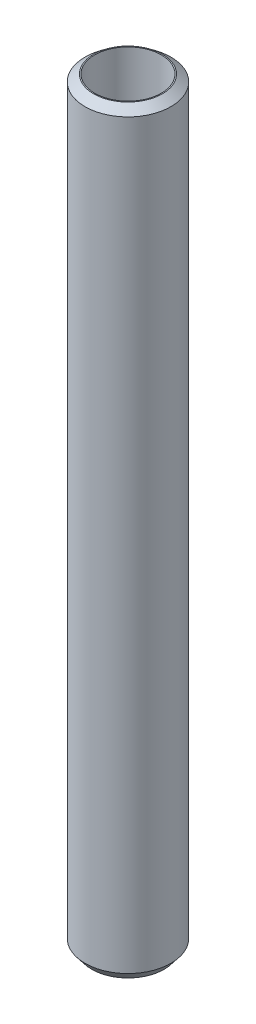
SolidWorks part; units mm, degrees
ref_plane "Front Plane" through (0, 0, 0) normal (0, 0, 1) x (1, 0, 0)
ref_plane "Top Plane" through (0, 0, 0) normal (0, 1, 0) x (1, 0, 0)
ref_plane "Right Plane" through (0, 0, 0) normal (1, 0, 0) x (0, 0, -1)
sketch "Sketch1" plane through (0, 0, 0) normal (0, 1, 0) x (1, 0, 0)
  circle A0 centre (0, 0) radius 27.5
  dimension "SHAFT_OD" = 55
extrude "Boss-Extrude1" add sketch "Sketch1" along normal blind 484.5993
sketch "Sketch2" plane through (0, 0, 0) normal (0, 1, 0) x (1, 0, 0)
  circle A0 centre (0, 0) radius 21.2874
  dimension "BORE_D" = 42.5747
extrude "Cut-Extrude1" cut sketch "Sketch2" along normal through all
chamfer "Chamfer1" distance 4.3285 angle 51.885 2 edges at (0, 484.5993, 27.5) (0, 0, 27.5) first distance on face at (0, 484.5993, 27.5) first distance on face at (0, 0, 21.2874)
